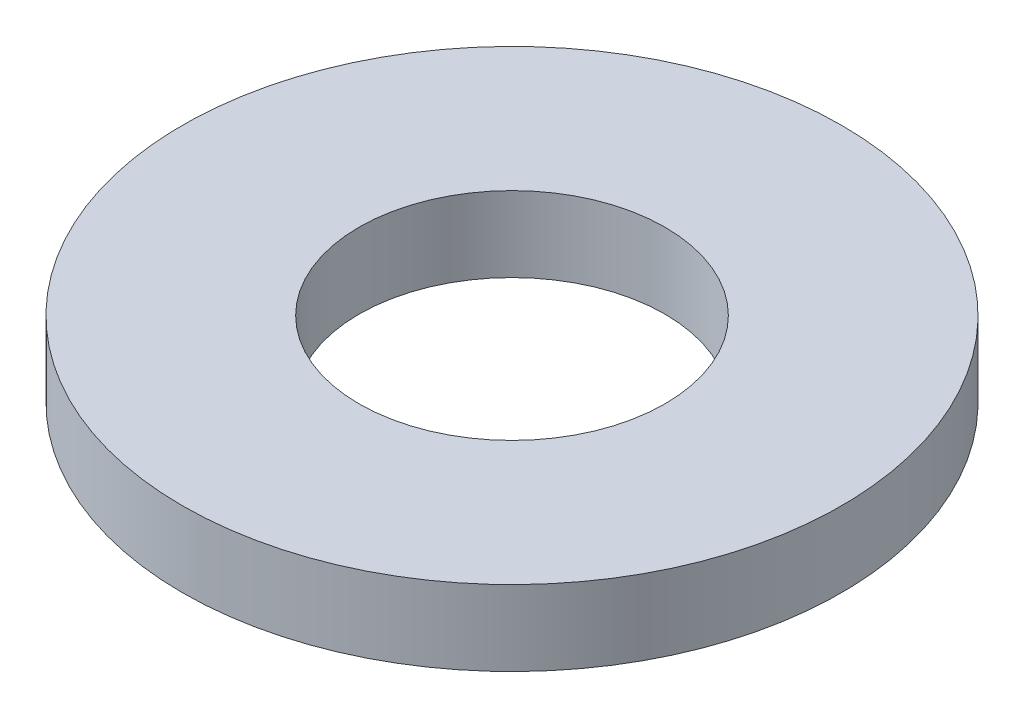
SolidWorks part; units mm, degrees
ref_plane "Front Plane" through (0, 0, 0) normal (0, 0, 1) x (1, 0, 0)
ref_plane "Top Plane" through (0, 0, 0) normal (0, 1, 0) x (1, 0, 0)
ref_plane "Right Plane" through (0, 0, 0) normal (1, 0, 0) x (0, 0, -1)
sketch "Sketch1" plane through (0, 0, 0) normal (0, 1, 0) x (1, 0, 0)
  circle A0 centre (0, 0) radius 70
  dimension "FLANGE_OD" = 140
extrude "Boss-Extrude1" add sketch "Sketch1" along normal blind 16
sketch "Sketch2" plane through (0, 0, 0) normal (0, 1, 0) x (1, 0, 0)
  circle A0 centre (0, 0) radius 32.5
  dimension "BORE_D" = 65
extrude "Cut-Extrude1" cut sketch "Sketch2" along normal through all
sketch "Sketch3" plane through (0, 16, 0) normal (0, 1, 0) x (1, 0, 0)
  circle A0 centre (0, 0) radius 28.1597 construction
  circle A1 centre (-28.1597, 0) radius 3.2846
  dimension "BOLT_D" = 6.5693
  dimension "BOLT_PCD" = 56.3195
extrude "Cut-Extrude2" cut sketch "Sketch3" against normal blind 14.9353 rebuild error yes
pattern_circular "CirPattern1" count 8 over 360 rebuild error yes
